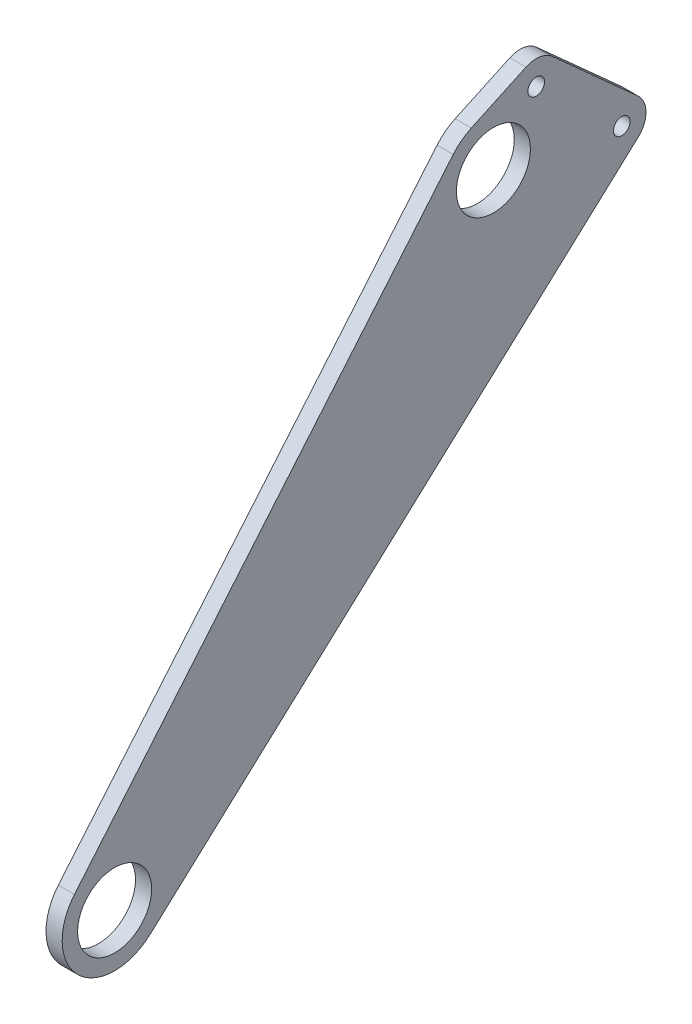
SolidWorks part; units mm, degrees
material "6061-T6 (SS)"
ref_plane "Front Plane" through (0, 0, 0) normal (0, 0, 1) x (1, 0, 0)
ref_plane "Top Plane" through (0, 0, 0) normal (0, 1, 0) x (1, 0, 0)
ref_plane "Right Plane" through (0, 0, 0) normal (1, 0, 0) x (0, 0, -1)
sketch "Sketch1" plane through (0, 0, 0) normal (1, 0, 0) x (0, 0, -1)
  line L0 (0, 0) -> (47.4141, 0) construction
  line L1 (0, 0) -> (143.6841, 143.6841) construction
  line L2 (143.6841, 143.6841) -> (148.964, 177.5652) construction
  line L3 (0, 0) -> (148.964, 177.5652) construction
  line L4 (0, 0) -> (199.4397, 167.3498) construction
  line L5 (148.964, 177.5652) -> (165.7989, 197.6325) construction
  line L6 (-15.8106, 13.2639) -> (133.1534, 190.8291)
  line L7 (140.2738, 196.2838) -> (161.7881, 206.2718)
  line L8 (172.1715, 204.7117) -> (205.8123, 174.429)
  line L9 (205.8681, 160.3212) -> (13.9282, -15.2286)
  circle A0 centre (0, 0) radius 14.5542
  circle A1 centre (143.6841, 143.6841) radius 14.5542 construction
  circle A2 centre (148.964, 177.5652) radius 14.5542
  circle A3 centre (199.4397, 167.3498) radius 3.2639
  circle A4 centre (165.7989, 197.6325) radius 3.2639
  arc A5 (172.1715, 204.7117) -> (161.7881, 206.2718) centre (165.7989, 197.6325) ccw
  arc A6 (205.8681, 160.3212) -> (205.8123, 174.429) centre (199.4397, 167.3498) ccw
  arc A7 (140.2738, 196.2838) -> (133.1534, 190.8291) centre (148.964, 177.5652) ccw
  arc A8 (13.9282, -15.2286) -> (-15.8106, 13.2639) centre (0, 0) cw
  dimension "D1" = 29.1084
  dimension "D4" = 34.29
  dimension "D5" = 29.1084
  dimension "D6" = 29.1084
  dimension "D10" = 6.5278
  dimension "D12" = 6.5278
  dimension "D13" = 9.525
  dimension "D14" = 9.525
  dimension "D15" = 20.6375
  dimension "D16" = 20.6375
  dimension "D2" = 45
  dimension "D3" = 203.2
  dimension "D7" = 231.775
  dimension "D8" = 260.35
  dimension "D9" = 40
  dimension "D11" = 26.1937
extrude "Boss-Extrude1" add sketch "Sketch1" along normal blind 6.35
